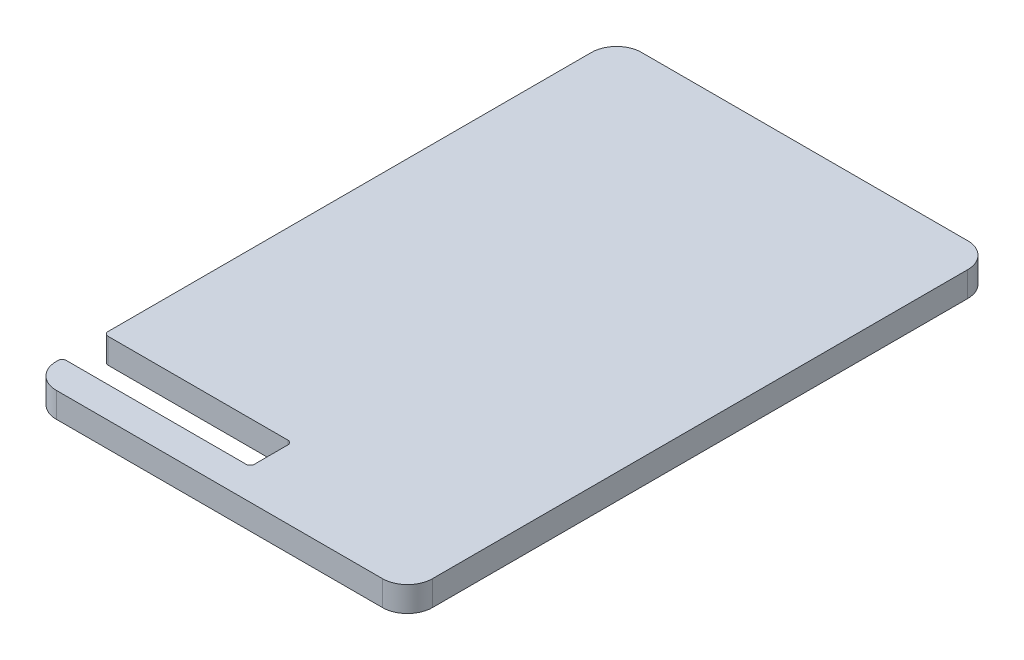
SolidWorks part; units mm, degrees
ref_plane "Alzado" through (0, 0, 0) normal (0, 0, 1) x (1, 0, 0)
ref_plane "Planta" through (0, 0, 0) normal (0, 1, 0) x (1, 0, 0)
ref_plane "Vista lateral" through (0, 0, 0) normal (1, 0, 0) x (0, 0, -1)
sketch "Croquis1" plane through (0, 0, 0) normal (0, 1, 0) x (1, 0, 0)
  line L1 (-22.5, 35.3062) -> (22.5, 35.3062)
  line L2 (-22.5, 35.3062) -> (-22.5, -34.6938)
  line L3 (-22.5, -34.6938) -> (22.5, -34.6938)
  line L4 (22.5, 35.3062) -> (22.5, -34.6938)
  dimension "D1" = 22.5
  dimension "D2" = 45
  dimension "D3" = 35.3062
  dimension "D4" = 70
extrude "Saliente-Extruir1" add sketch "Croquis1" along normal blind 3
sketch "Croquis2" plane through (0, 3, 0) normal (0, 1, 0) x (1, 0, 0)
  line L0 (-22.5, 35.3062) -> (-22.5, -34.6938) construction
  line L1 (-22.5, -26) -> (0, -26)
  line L2 (-22.5, -26) -> (-22.5, -31)
  line L3 (-22.5, -31) -> (0, -31)
  line L4 (0, -26) -> (0, -31)
  dimension "D1" = 5
  dimension "D2" = 31
  dimension "D3" = 22.5
extrude "Cortar-Extruir1" cut sketch "Croquis2" against normal up to surface (3 mm away) up to face at (0, 0, -0.3062)
fillet "Redondeo1" radius 3 4 edges at (-22.5, 1.5, 34.6938) (22.5, 1.5, 34.6938) (-22.5, 1.5, -35.3062) (22.5, 1.5, -35.3062)
fillet "Redondeo2" radius 0.5 4 edges at (-22.5, 1.5, 31) (0, 1.5, 31) (0, 1.5, 26) (-22.5, 1.5, 26)
